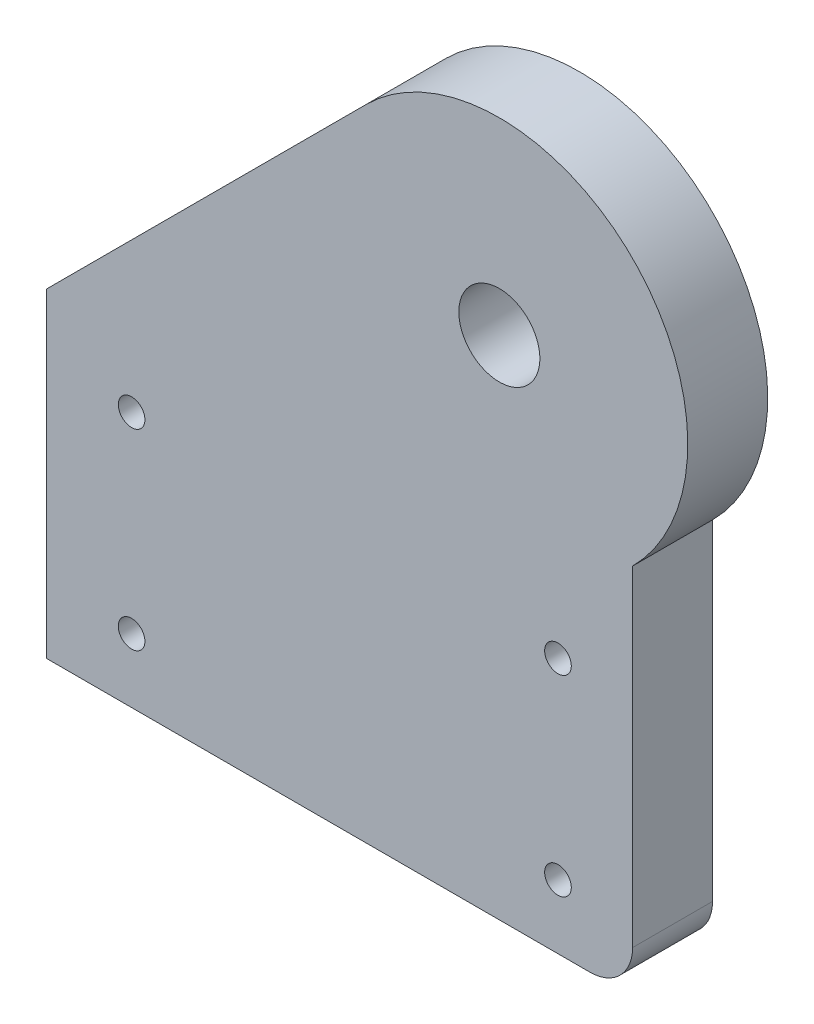
SolidWorks part; units mm, degrees
ref_plane "Front Plane" through (0, 0, 0) normal (0, 0, 1) x (1, 0, 0)
ref_plane "Top Plane" through (0, 0, 0) normal (0, 1, 0) x (1, 0, 0)
ref_plane "Right Plane" through (0, 0, 0) normal (1, 0, 0) x (0, 0, -1)
sketch "Sketch1" plane through (0, 0, 0) normal (0, 0, 1) x (1, 0, 0)
  line L0 (0, 38.1) -> (38.1, 76.2)
  line L1 (0, 0) -> (35.5012, 0)
  line L2 (0, 0) -> (0, 38.1)
  line L8 (38.1, 76.2) -> (69.85, 44.45) construction
  line L9 (35.5012, 0) -> (69.85, 0)
  line L12 (69.85, 0) -> (69.85, 44.45)
  arc A0 (38.1, 76.2) -> (69.85, 44.45) centre (53.975, 60.325) cw
  circle A2 centre (53.975, 60.325) radius 4.826
  point P0 (0, 0)
  dimension "D6" = 38.1
  dimension "D5" = 0
  dimension "D7" = 9.652
  dimension "D1" = 38.1
  dimension "D2" = 44.45
  dimension "D3" = 90
  dimension "D4" = 69.85
extrude "Boss-Extrude4" add sketch "Sketch1" along normal blind 9.525 contours L1 L2 | A0 L0 A2 region at (39.6815, 35.8136, 0)
sketch "Sketch2" plane through (0, 0, 9.525) normal (0, 0, 1) x (1, 0, 0)
  line L1 (10.16, 7.62) -> (60.96, 7.62) construction
  line L2 (10.16, 7.62) -> (10.16, 30.48) construction
  line L3 (10.16, 30.48) -> (60.96, 30.48) construction
  line L4 (60.96, 7.62) -> (60.96, 30.48) construction
  line L5 (0, 0) -> (69.85, 0) construction
  line L6 (69.85, 0) -> (69.85, 44.45) construction
  circle A0 centre (10.16, 30.48) radius 1.5875
  circle A1 centre (60.96, 30.48) radius 1.5875
  circle A2 centre (60.96, 7.62) radius 1.5875
  circle A3 centre (10.16, 7.62) radius 1.5875
  dimension "D5" = 3.175
  dimension "D6" = 3.175
  dimension "D7" = 3.175
  dimension "D8" = 3.175
  dimension "D1" = 22.86
  dimension "D2" = 50.8
  dimension "D3" = 8.89
  dimension "D4" = 7.62
extrude "Cut-Extrude2" cut sketch "Sketch2" against normal up to surface (9.525 mm away) contours A0 | A3 | A1 | A2 up to face at (58.801, 60.325, 0)
fillet "Fillet1" radius 5.08 1 edges at (69.85, 0, 4.7625)
